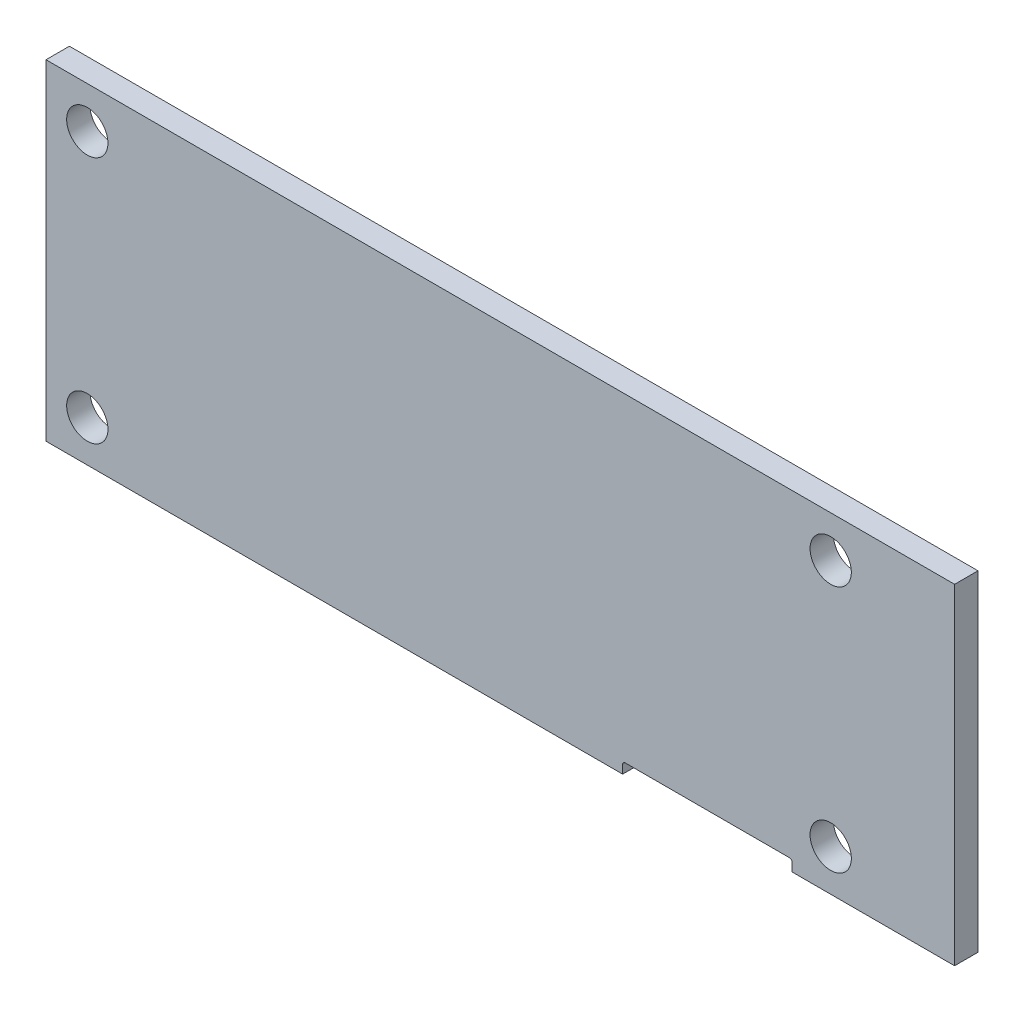
SolidWorks part; units mm, degrees
ref_plane "Ön Düzlem" through (0, 0, 0) normal (0, 0, 1) x (1, 0, 0)
ref_plane "Üst Düzlem" through (0, 0, 0) normal (0, 1, 0) x (1, 0, 0)
ref_plane "Sağ Düzlem" through (0, 0, 0) normal (1, 0, 0) x (0, 0, -1)
sketch "Çizim2" plane through (0, 0, 0) normal (0, 0, 1) x (1, 0, 0)
  line L0 (0, 0) -> (-3.7878, 0) construction
  line L1 (-35.5862, -12.7) -> (34.2638, -12.7)
  line L2 (-35.5862, -12.7) -> (-35.5862, 12.7)
  line L3 (-35.5862, 12.7) -> (34.2638, 12.7)
  line L4 (34.2638, -12.7) -> (34.2638, 12.7)
  line L13 (0, 0) -> (0, 8.8666) construction
  line L14 (-32.4112, 0) -> (24.7388, 0) construction
  line L15 (34.2638, 0) -> (24.7388, 0) construction
  line L16 (-24.4949, -9.525) -> (-24.4949, -12.7) construction
  line L17 (24.7388, 9.525) -> (-32.4112, 9.525) construction
  line L18 (24.7388, 9.525) -> (24.7388, -9.525) construction
  line L19 (24.7388, -9.525) -> (-32.4112, -9.525) construction
  line L20 (-32.4112, 9.525) -> (-32.4112, -9.525) construction
  line L21 (-24.7262, 12.7) -> (-24.7262, 9.525) construction
  circle A2 centre (24.7388, 9.525) radius 1.5875
  circle A3 centre (-32.4112, 9.525) radius 1.5875
  circle A4 centre (-32.4112, -9.525) radius 1.5875
  circle A5 centre (24.7388, -9.525) radius 1.5875
  point P0 (0, 0)
  point P8 (0, 0)
  point P13 (24.7388, 0)
  dimension "D3" = 57.15
  dimension "D5" = 3.175
  dimension "D1" = 69.85
  dimension "D2" = 25.4
  dimension "D4" = 19.05
  dimension "D6" = 9.525
extrude "Yükseklik-Ekstrüzyon1" add sketch "Çizim2" along normal blind 1.8
sketch "Çizim6" plane through (0, 0, 0) normal (0, 0, -1) x (-1, 0, 0)
  line L0 (15.769, 412.5358) -> (15.769, 276.0493) construction
sketch "Çizim7" plane through (0, 0, 0) normal (0, 0, -1) x (-1, 0, 0)
  line L0 (-34.2638, -12.7) -> (-34.2638, 12.7) construction
  line L1 (-34.2638, 8.01) -> (-27.3638, 8.01)
  line L2 (-34.2638, 8.01) -> (-34.2638, -8.01)
  line L3 (-34.2638, -8.01) -> (-27.3638, -8.01)
  line L4 (-27.3638, 8.01) -> (-27.3638, -8.01)
  line L5 (-34.2638, 12.7) -> (35.5862, 12.7) construction
  line L6 (-22.3704, 12.7) -> (-9.9452, 12.7)
  line L7 (10.6339, -9.22) -> (12.8628, -6.9911)
  line L8 (-5.7736, 9.4161) -> (12.8628, 9.4161)
  line L9 (-5.7736, 9.4161) -> (-5.7736, -9.22)
  line L10 (-5.7736, -9.22) -> (10.6339, -9.22)
  line L11 (12.8628, 9.4161) -> (12.8628, -6.9911)
  line L12 (-22.3704, 12.7) -> (-22.3704, 7.1096)
  line L13 (-22.3704, 7.1096) -> (-9.9452, 7.1096)
  line L14 (-9.9452, 12.7) -> (-9.9452, 7.1096)
  line L15 (-34.2638, 12.7) -> (-43.7423, 12.7) construction
  line L16 (-19.615, 0.1006) -> (-7.0141, 0.1006) construction
  line L17 (23.1396, 2.656) -> (23.5016, 2.294)
  line L18 (19.7882, 12.7) -> (28.6635, 12.7)
  line L19 (19.7882, 12.7) -> (19.7882, 7.4617)
  line L20 (19.7882, 7.4617) -> (28.6635, 7.4617)
  line L21 (28.6635, 12.7) -> (28.6635, 7.4617)
  line L22 (23.5016, 2.294) -> (24.1832, 3.843)
  line L23 (24.1832, 6.1832) -> (24.1832, -5.1082) construction
  line L24 (23.1396, 2.656) -> (24.1832, 6.0238)
  line L25 (23.034, 2.294) -> (24.1832, 0.8)
  line L26 (23.034, 2.294) -> (21.0686, -4.0616)
  line L27 (21.0686, -4.0616) -> (19.7882, -5.2229)
  line L28 (19.7882, -5.2229) -> (22.2368, -5.2229)
  line L29 (22.2368, -5.2229) -> (23.5016, -3.9581)
  line L30 (23.5016, -3.9581) -> (23.5016, 0.8)
  line L31 (23.5016, 0.8) -> (24.1832, 0.3396)
  line L32 (24.8648, 0.8) -> (24.1832, 0.3396)
  line L33 (24.8648, -3.9581) -> (24.8648, 0.8)
  line L34 (26.1296, -5.2229) -> (24.8648, -3.9581)
  line L35 (28.5782, -5.2229) -> (26.1296, -5.2229)
  line L36 (27.2977, -4.0616) -> (28.5782, -5.2229)
  line L37 (25.3324, 2.294) -> (27.2977, -4.0616)
  line L38 (25.3324, 2.294) -> (24.1832, 0.8)
  line L39 (25.2268, 2.656) -> (24.1832, 6.0238)
  line L40 (24.8648, 2.294) -> (24.1832, 3.843)
  line L41 (25.2268, 2.656) -> (24.8648, 2.294)
  line L42 (35.5862, -12.7) -> (-34.2638, -12.7) construction
  line L43 (14.1965, -7.3586) -> (29.2853, -7.3586)
  line L44 (14.1965, -7.3586) -> (14.1965, -12.7)
  line L45 (14.1965, -12.7) -> (29.2853, -12.7)
  line L46 (29.2853, -7.3586) -> (29.2853, -12.7)
  line L47 (-25.8308, 3.1123) -> (-21.2171, 3.1123)
  line L48 (-25.8308, 3.1123) -> (-25.8308, -2.9201)
  line L49 (-25.8308, -2.9201) -> (-21.2171, -2.9201)
  line L50 (-21.2171, 3.1123) -> (-21.2171, -2.9201)
  line L51 (-43.7423, 12.7) -> (-43.7423, -12.7) construction
  line L52 (-34.2638, -12.7) -> (-43.7423, -12.7) construction
  line L53 (-43.7423, 0) -> (-30.6857, 0) construction
  circle A0 centre (-13.3146, 0.1006) radius 6.259
  dimension "D1" = 8.01
  dimension "D2" = 8.01
  dimension "D3" = 6.9
wrap "Sar1" sketch "Çizim7" wrap type scribe source sketch "Çizim7" face at (-30.8237, -9.525, 0)
sketch "Çizim8" plane through (0, 0, 0) normal (0, 0, -1) x (-1, 0, 0)
  line L0 (-33.6466, 11.7385) -> (-33.6466, 8.5596) construction
  line L1 (-27.011, 7.912) -> (-27.011, 3.1592) construction
  line L2 (-27.011, 1.646) -> (-27.011, -1.1557) construction
  line L3 (-27.011, -2.6286) -> (-27.011, -7.8367) construction
  line L4 (-20.7637, 2.8365) -> (-20.7637, -2.9472) construction
  line L5 (-7.9415, 9.6929) -> (7.9991, 9.6929) construction
  line L6 (14.7804, 9.7524) -> (8.9908, 9.7524) construction
  line L7 (24.2759, 5.9783) -> (28.981, 5.9783) construction
  line L8 (20.6427, -7.0153) -> (30.3873, -7.0153) construction
  text T0 "GND" font "Mongolian Baiti" height in points 4
  text T1 "switch" font "Century Gothic" height in points 4
  text T2 "main" font "Century Gothic" height in points 4
  text T3 "apogee" font "Century Gothic" height in points 4
  text T4 "battery" font "Century Gothic" height in points 4
  text T5 "TeleMetrum" font "@Malgun Gothic Semilight" height 2.54
  text T6 "v" font "Century Gothic" height in points 5
  text T7 "4.0" font "Century Gothic" height in points 8
  text T8 "debug" font "Century Gothic" height in points 5
  text T9 "companion" font "Century Gothic" height in points 4
wrap "Sar3" sketch "Çizim8" wrap type scribe source sketch "Çizim8" face at (0.0687, 1.9913, 0)
sketch "Çizim9" plane through (0, 0, 0) normal (0, 0, -1) x (-1, 0, 0)
  line L1 (-34.2638, 8.01) -> (-27.3638, 8.01)
  line L3 (-34.2638, -8.01) -> (-27.3638, -8.01)
  line L4 (-27.3638, 8.01) -> (-27.3638, -8.01)
  line L5 (-34.0638, 7.81) -> (-27.5638, 7.81)
  line L7 (-34.0638, -7.81) -> (-27.5638, -7.81)
  line L8 (-27.5638, 7.81) -> (-27.5638, -7.81)
  line L9 (-13.3146, 6.3596) -> (-13.3146, -6.1584) construction
  line L10 (10.5116, -8.7762) -> (12.4233, -6.8645)
  line L11 (-5.3275, 8.9725) -> (12.4233, 8.9725)
  line L12 (10.6339, -9.22) -> (12.8628, -6.9911)
  line L13 (-5.7736, 9.4161) -> (12.8628, 9.4161)
  line L14 (-5.7736, 9.4161) -> (-5.7736, -9.22)
  line L15 (-5.7736, -9.22) -> (10.6339, -9.22)
  line L16 (12.8628, 9.4161) -> (12.8628, -6.9911)
  line L17 (-5.3275, 8.9725) -> (-5.3275, -8.7762)
  line L18 (-5.3275, -8.7762) -> (10.5116, -8.7762)
  line L19 (12.4233, 8.9725) -> (12.4233, -6.8645)
  line L20 (29.1023, -12.7) -> (29.2853, -12.7)
  line L21 (14.1965, -7.3586) -> (29.2853, -7.3586)
  line L22 (14.1965, -7.3586) -> (14.1965, -12.7)
  line L23 (14.1965, -12.7) -> (14.3743, -12.7)
  line L24 (29.2853, -7.3586) -> (29.2853, -12.7)
  line L25 (14.3743, -7.5343) -> (29.1023, -7.5343)
  line L26 (14.3743, -7.5343) -> (14.3743, -12.7)
  line L28 (29.1023, -7.5343) -> (29.1023, -12.7)
  line L29 (28.4095, 12.7) -> (28.6635, 12.7)
  line L30 (19.7882, 12.7) -> (20.0422, 12.7)
  line L31 (19.7882, 12.7) -> (19.7882, 7.4617)
  line L32 (19.7882, 7.4617) -> (28.6635, 7.4617)
  line L33 (28.6635, 12.7) -> (28.6635, 7.4617)
  line L35 (20.0422, 12.7) -> (20.0422, 7.7305)
  line L36 (20.0422, 7.7305) -> (28.4095, 7.7305)
  line L37 (28.4095, 12.7) -> (28.4095, 7.7305)
  line L38 (-34.2638, 8.01) -> (-34.2638, -8.01)
  line L39 (-25.8308, 3.1123) -> (-21.2171, 3.1123)
  line L40 (-25.8308, 3.1123) -> (-25.8308, -2.9201)
  line L41 (-25.8308, -2.9201) -> (-21.2171, -2.9201)
  line L42 (-21.2171, 3.1123) -> (-21.2171, -2.9201)
  line L43 (-25.7496, 3.0263) -> (-21.2982, 3.0263)
  line L44 (-25.7496, 3.0263) -> (-25.7496, -2.8388)
  line L45 (-25.7496, -2.8388) -> (-21.2982, -2.8388)
  line L46 (-21.2982, 3.0263) -> (-21.2982, -2.8388)
  line L47 (-22.3704, 12.7) -> (-9.9452, 12.7)
  line L48 (-22.3704, 12.7) -> (-22.3704, 7.1096)
  line L49 (-22.3704, 7.1096) -> (-9.9452, 7.1096)
  line L50 (-9.9452, 12.7) -> (-9.9452, 7.1096)
  line L58 (-34.0638, 7.81) -> (-34.0638, -7.81)
  line L59 (-27.3638, 8.01) -> (-34.2638, 8.01) construction
  circle A0 centre (-13.3146, 0.1006) radius 6.259 construction
  circle A1 centre (-13.3146, 0.1006) radius 6.259
  circle A2 centre (-13.3146, 0.1006) radius 5.9925
  dimension "D1" = 6.5
  dimension "D2" = 0.254
  dimension "D3" = 0.254
  dimension "D4" = 0.2
  dimension "D5" = 0.2
  dimension "D6" = 0.2
  dimension "D7" = 0.2
wrap "Sar7" sketch "Çizim9" wrap type scribe source sketch "Çizim9" face at (0.0687, 1.9913, 0)
sketch "Çizim11" plane through (0, 0, 0) normal (0, 0, -1) x (-1, 0, 0)
  line L0 (-4.2018, 103.1344) -> (417.1315, 103.1344) construction
  line L1 (-21.7744, -12.0505) -> (-21.7744, -12.7)
  line L2 (-21.5744, -11.8505) -> (-8.9458, -11.8505)
  line L3 (-8.7458, -12.7) -> (-8.7458, -12.0505)
  line L5 (-21.7744, -12.7) -> (-8.7458, -12.7)
  arc A0 (-8.7458, -12.0505) -> (-8.9458, -11.8505) centre (-8.9458, -12.0505) ccw
  arc A1 (-21.7744, -12.0505) -> (-21.5744, -11.8505) centre (-21.5744, -12.0505) cw
  dimension "D1" = 0.2
extrude "Kes-Ekstrüzyon1" cut sketch "Çizim11" against normal blind 10
sketch "Çizim13" plane through (0, 0, 0) normal (0, 0, -1) x (-1, 0, 0)
  line L0 (175.9277, 29.1122) -> (175.9277, -134.2211) construction
sketch "Çizim14" plane through (0, 0, 0) normal (0, 0, -1) x (-1, 0, 0)
  line L0 (70.4165, 82.6929) -> (491.0831, 82.6929) construction
  line L1 (-536.4231, 132.8819) -> (-115.7564, 132.8819) construction
  line L2 (-24.7388, 9.525) -> (32.4112, 9.525) construction
  line L3 (3.8362, 9.525) -> (3.8362, -7.5166) construction
  line L4 (-24.7388, 9.525) -> (-24.7388, -9.525) construction
  line L5 (-24.7388, 0) -> (24.5695, 0) construction
  circle A0 centre (-24.7388, 9.525) radius 1.5875
  circle A1 centre (-24.7388, 9.525) radius 2.5997
  circle A2 centre (-24.7388, -9.525) radius 1.5875
  circle A3 centre (32.4112, -9.525) radius 1.5875
  circle A4 centre (32.4112, 9.525) radius 1.5875
  circle A5 centre (32.4112, 9.525) radius 2.5997
  circle A6 centre (32.4112, -9.525) radius 2.5997
  circle A7 centre (-24.7388, -9.525) radius 2.5997
wrap "Sar9" sketch "Çizim14" wrap type scribe source sketch "Çizim14" face at (3.5744, -1.2805, 0)
sketch "Sketch1" plane through (0, 0, 0) normal (0, 0, -1) x (-1, 0, 0)
  line L0 (-23.5239, 3.0263) -> (-23.5239, -2.8388) construction
  line L1 (-21.2982, 3.0263) -> (-25.7496, 3.0263) construction
  line L2 (-25.7496, -2.8388) -> (-21.2982, -2.8388) construction
  line L3 (-23.5239, 3.0263) -> (-23.5239, 3.5066) construction
  line L4 (-23.5239, 0.0938) -> (-21.9397, 0.0938) construction
  line L5 (-23.6239, 3.5066) -> (-23.4239, 3.5066)
  line L6 (-23.6239, 3.5066) -> (-23.6239, 4.4066)
  line L7 (-23.6239, 5.5066) -> (-23.4239, 5.5066)
  line L8 (-23.4239, 3.5066) -> (-23.4239, 4.4066)
  line L11 (-24.5239, 4.4066) -> (-23.6239, 4.4066)
  line L12 (-24.5239, 4.4066) -> (-24.5239, 4.6066)
  line L13 (-24.5239, 4.6066) -> (-23.6239, 4.6066)
  line L14 (-22.5239, 4.4066) -> (-22.5239, 4.6066)
  line L17 (-23.6239, -5.319) -> (-23.4239, -3.319) construction
  line L18 (-23.6239, -3.319) -> (-23.4239, -5.319) construction
  line L19 (-23.5239, -2.8388) -> (-23.5239, -5.7993) construction
  line L20 (-23.4239, -3.319) -> (-23.4239, -5.319)
  line L21 (-23.6239, -5.319) -> (-23.4239, -5.319)
  line L22 (-23.6239, -3.319) -> (-23.6239, -5.319)
  line L23 (-23.6239, -3.319) -> (-23.4239, -3.319)
  line L24 (-23.4239, 4.6066) -> (-23.4239, 5.5066)
  line L25 (-23.4239, 4.6066) -> (-22.5239, 4.6066)
  line L26 (-23.5239, 5.5066) -> (-23.5239, 5.9869) construction
  line L28 (-23.6239, 4.6066) -> (-23.6239, 5.5066)
  line L32 (-23.4239, 4.4066) -> (-22.5239, 4.4066)
  point P6 (-23.5239, 4.5066)
  point P12 (-23.5239, 4.5066)
  dimension "D1" = 0.2
  dimension "D2" = 0.2
  dimension "D3" = 2
  dimension "D4" = 2
wrap "Wrap1" sketch "Sketch1" wrap type scribe source sketch "Sketch1" face at (3.5744, -1.2805, 0)
